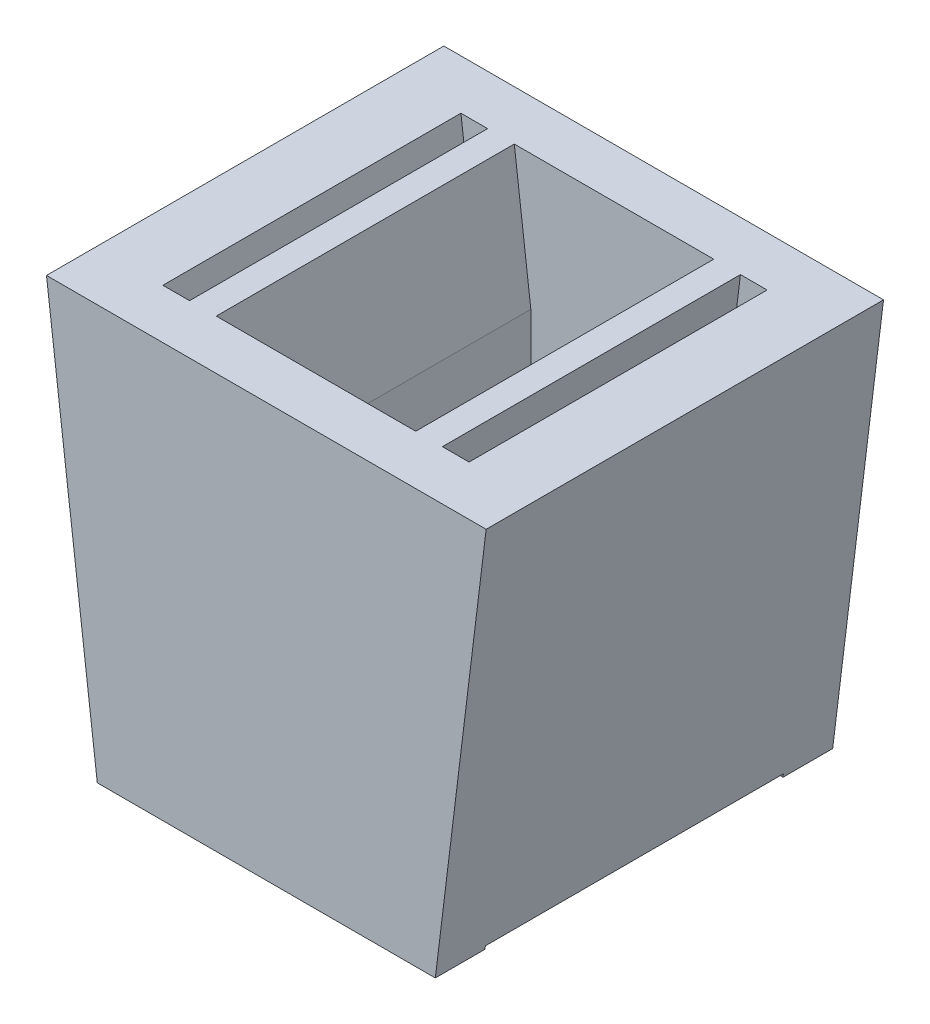
SolidWorks part; units mm, degrees
ref_plane "Alzado" through (0, 0, 0) normal (0, 0, 1) x (1, 0, 0)
ref_plane "Planta" through (0, 0, 0) normal (0, 1, 0) x (1, 0, 0)
ref_plane "Vista lateral" through (0, 0, 0) normal (1, 0, 0) x (0, 0, -1)
sketch "Croquis1" plane through (0, 0, 0) normal (0, 0, 1) x (1, 0, 0)
  line L0 (11.5593, 31.0171) -> (16.5969, 31.0171)
  line L1 (0, 0) -> (0, 2.0721) construction
  line L2 (-2.0148, -31.2573) -> (-1.9564, -30.7815) construction
  line L3 (-1.9275, -31.0171) -> (-1.9564, -30.7815) construction
  line L4 (11.5593, 31.0171) -> (7.7214, -0.2402)
  line L5 (7.7214, -0.2402) -> (12.7884, 0)
  line L6 (16.5969, 31.0171) -> (12.7884, 0)
  line L8 (-7.5293, 31.0171) -> (-6.2793, 20.8365)
  line L9 (-11.5593, 31.0171) -> (-7.7214, -0.2402)
  line L10 (-6.2793, 20.8365) -> (-6.2793, 4.4255)
  line L11 (-8.2643, 20.5927) -> (-9.5443, 31.0171)
  line L12 (-6.2793, 4.4255) -> (-8.2643, 20.5927)
  line L13 (-16.5969, 31.0171) -> (-12.7884, 0)
  line L14 (-7.5293, 31.0171) -> (-9.5443, 31.0171)
  line L15 (-11.5593, 31.0171) -> (-16.5969, 31.0171)
  line L16 (7.5293, 31.0171) -> (6.2793, 20.8365)
  line L17 (6.2793, 20.8365) -> (6.2793, 4.4255)
  line L18 (6.2793, 4.4255) -> (8.2643, 20.5927)
  line L19 (-7.7214, -0.2402) -> (-12.7884, 0)
  line L20 (8.2643, 20.5927) -> (9.5443, 31.0171)
  line L21 (7.5293, 31.0171) -> (9.5443, 31.0171)
  point P4 (0, 0)
  point P9 (3.75, 0)
  point P13 (-3.75, 0)
  point P16 (-3.75, 0)
  point P17 (3.75, 0)
  point P18 (7.5584, 31.0171)
  dimension "D1" = 5
  dimension "D2" = 62.5
  dimension "D4" = 7
  dimension "D5" = 7
  dimension "D6" = 2
  dimension "D7" = 2
extrude "Saliente-Extruir1" add sketch "Croquis1" along normal blind 30
sketch "Croquis3" plane through (0, 0, 0) normal (1, 0, 0) x (0, 0, -1)
  line L1 (-30, 31.0171) -> (-26.25, 31.0171)
  line L2 (-30, 31.0171) -> (-30, -0.2402)
  line L3 (-30, -0.2402) -> (-26.25, -0.2402)
  line L4 (-26.25, 31.0171) -> (-26.25, -0.2402)
  line L5 (-30, -0.2402) -> (0, -0.2402) construction
  line L7 (0, 31.0171) -> (-3.75, 31.0171)
  line L8 (0, 31.0171) -> (0, -0.2402)
  line L9 (0, -0.2402) -> (-3.75, -0.2402)
  line L10 (-3.75, 31.0171) -> (-3.75, -0.2402)
  dimension "D1" = 31.2573
  dimension "D2" = 22.5
  dimension "D3" = 31.2573
  dimension "D4" = 3.75
extrude "Saliente-Extruir3" add sketch "Croquis3" along normal up to surface and the other way up to surface up to face at (14.6927, 15.5085, 15) other way up to face at (-14.6927, 15.5085, 15)
